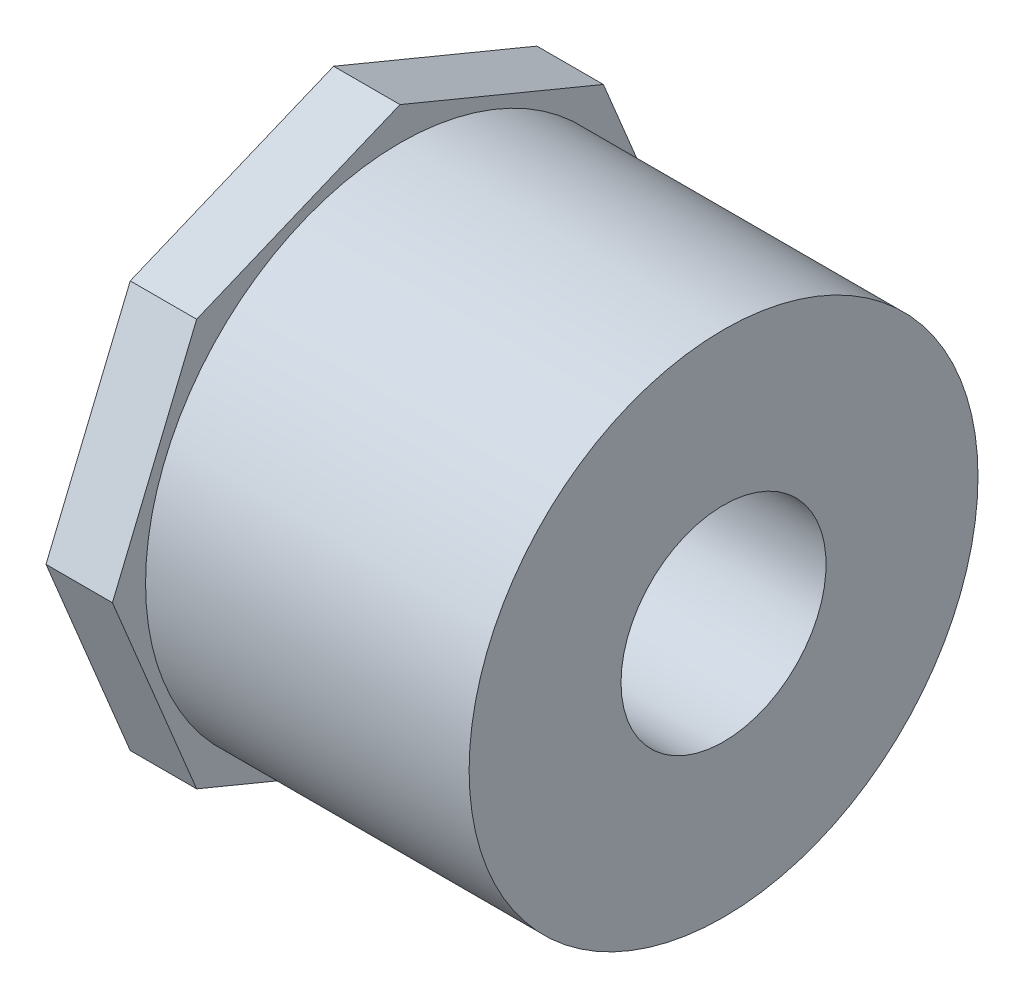
SolidWorks part; units mm, degrees
ref_plane "Front Plane" through (0, 0, 0) normal (0, 0, 1) x (1, 0, 0)
ref_plane "Top Plane" through (0, 0, 0) normal (0, 1, 0) x (1, 0, 0)
ref_plane "Right Plane" through (0, 0, 0) normal (1, 0, 0) x (0, 0, -1)
sketch "Sketch0" plane through (0, 0, 0) normal (0, 0, 1) x (1, 0, 0)
  line L0 (-46.228, 0) -> (0, 0) construction
  line L2 (-38.1, 30.1625) -> (-38.1, -30.1625) construction
  line L3 (-38.354, 31.496) -> (-38.354, -31.496) construction
  line L5 (-17.78, 16.637) -> (-46.228, 16.8275) construction
  line L6 (-17.78, 16.637) -> (-17.78, -16.637) construction
  line L7 (-17.78, -16.637) -> (-46.228, -16.8275) construction
  line L8 (-46.228, 16.8275) -> (-46.228, -16.8275) construction
  line L14 (-17.78, 12.1539) -> (-17.78, -12.1539) construction
  line L21 (-46.228, 0) -> (-17.78, 0) construction
  point P12 (-38.1, 0)
  point P27 (-38.354, 0)
  dimension "A" = 46.228
  dimension "OD A 2" = 33.655
  dimension "OD B 2" = 33.274
  dimension "ID 2" = 24.3078
  dimension "B" = 17.78
  dimension "Pipe OD 1" = 60.325
  dimension "C 1" = 38.1
  dimension "J" = 62.992
  dimension "K" = 7.874
sketch "Sketch1" plane through (0, 0, 0) normal (0, 0, 1) x (1, 0, 0)
  line L0 (-46.228, 0) -> (0, 0) construction
  line L1 (-46.228, 0) -> (0, 0) construction
  line L2 (-46.228, -30.1625) -> (0, -30.1625)
  line L3 (0, -12.1539) -> (0, -30.1625)
  line L4 (-46.228, -30.1625) -> (-46.228, -16.8275)
  line L5 (-46.228, -16.8275) -> (-17.78, -16.637)
  line L6 (0, 0) -> (0, -12.1539) construction
  line L8 (-17.78, -12.1539) -> (-17.78, -16.637)
  line L11 (-17.78, -12.1539) -> (0, -12.1539)
revolve "Revolve1" add sketch "Sketch1" angle 360 about L1
sketch "Sketch2" plane through (-46.228, 0, 0) normal (-1, 0, 0) x (0, 0, 1)
  line L0 (0, 0) -> (0, 36.3684) construction
  line L1 (0, 36.3684) -> (-31.496, 18.1842) construction
  line L2 (-31.496, 18.1842) -> (-31.496, -18.1842) construction
  line L3 (-31.496, -18.1842) -> (0, -36.3684) construction
  line L4 (0, -36.3684) -> (31.496, -18.1842) construction
  line L5 (31.496, -18.1842) -> (31.496, 18.1842) construction
  line L6 (31.496, 18.1842) -> (0, 36.3684) construction
  line L8 (0, 34.091) -> (-24.106, 24.106)
  line L9 (-24.106, 24.106) -> (-34.091, 0)
  line L10 (-34.091, 0) -> (-24.106, -24.106)
  line L11 (-24.106, -24.106) -> (0, -34.091)
  line L12 (0, -34.091) -> (24.106, -24.106)
  line L13 (24.106, -24.106) -> (34.091, 0)
  line L14 (34.091, 0) -> (24.106, 24.106)
  line L15 (24.106, 24.106) -> (0, 34.091)
  circle A0 centre (0, 0) radius 16.8275 construction
  circle A1 centre (0, 0) radius 16.8275
  circle A2 centre (0, 0) radius 31.496 construction
  circle A3 centre (0, 0) radius 31.496 construction
  point P3 (0, 31.496)
extrude "Boss-Extrude1" add sketch "Sketch2" against normal up to vertex (7.874 mm away) up to point (-38.354, 0, 0)
other "CPoint1" parameters "Diameter"=25.4, "StubLength"=76.2
ref_axis "Axis1" through (-27.78, 0, 0) along (1, 0, 0)
other "CPoint2" parameters "Diameter"=50.8, "StubLength"=76.2
ref_axis "Axis2" through (-28.354, 0, 0) along (-1, 0, 0)
other "RPoint1"
ref_axis "Vertical" through (-38.354, 31.496, 0) along (0, -1, 0)
